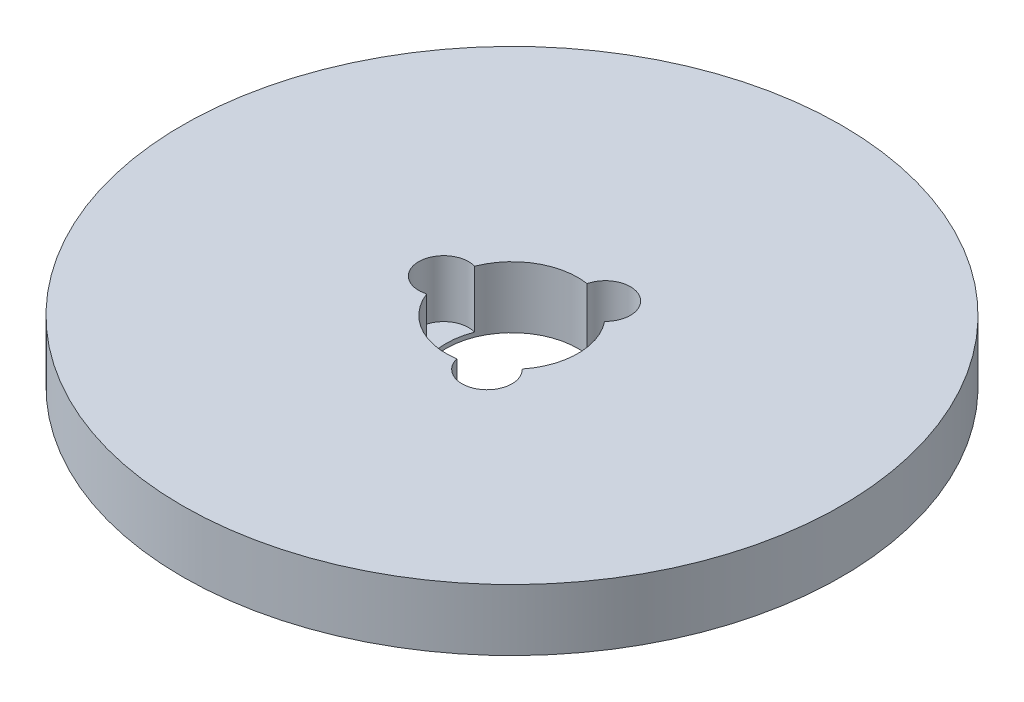
SolidWorks part; units mm, degrees
ref_plane "Front Plane" through (0, 0, 0) normal (0, 0, 1) x (1, 0, 0)
ref_plane "Top Plane" through (0, 0, 0) normal (0, 1, 0) x (1, 0, 0)
ref_plane "Right Plane" through (0, 0, 0) normal (1, 0, 0) x (0, 0, -1)
sketch "Sketch1" plane through (0, 0, 0) normal (0, 1, 0) x (1, 0, 0)
  circle A0 centre (0, 0) radius 75
  dimension "FLANGE_OD" = 150
extrude "Boss-Extrude1" add sketch "Sketch1" along normal blind 14
sketch "Sketch2" plane through (0, 0, 0) normal (0, 1, 0) x (1, 0, 0)
  circle A0 centre (0, 0) radius 15
  dimension "BORE_D" = 30
extrude "Cut-Extrude1" cut sketch "Sketch2" along normal through all
sketch "Sketch3" plane through (0, 14, 0) normal (0, 1, 0) x (1, 0, 0)
  circle A0 centre (0, 0) radius 15.5518 construction
  circle A1 centre (-15.5518, 0) radius 5.6828
  dimension "BOLT_D" = 11.3657
  dimension "BOLT_PCD" = 31.1036
extrude "Cut-Extrude2" cut sketch "Sketch3" against normal blind 12.9987
pattern_circular "CirPattern1" count 3 over 360 about axis through (0, 0, 0) along (0, 1, 0) of "Cut-Extrude2"
